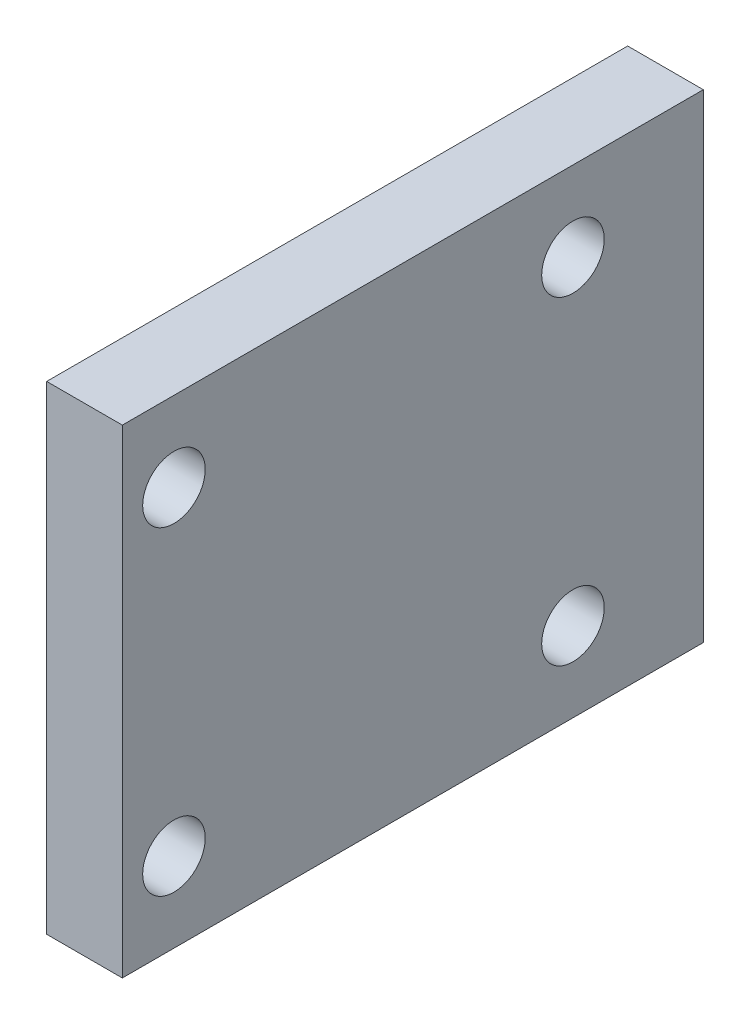
SolidWorks part; units mm, degrees
material "6061 Alloy"
ref_plane "Front Plane" through (0, 0, 0) normal (0, 0, 1) x (1, 0, 0)
ref_plane "Top Plane" through (0, 0, 0) normal (0, 1, 0) x (1, 0, 0)
ref_plane "Right Plane" through (0, 0, 0) normal (1, 0, 0) x (0, 0, -1)
sketch "Sketch2" plane through (-488.9654, 0, 0) normal (1, 0, 0) x (0, 0, -1)
  line L1 (194.9873, 128.4838) -> (194.9873, 166.5838)
  line L2 (194.9873, 126.5338) -> (194.9873, 131.5338) construction
  line L3 (210.0161, 128.4838) -> (140.1661, 128.4838) construction
  line L4 (194.9873, 167.5338) -> (194.9873, 165.7338) construction
  line L5 (140.1661, 166.5838) -> (210.0161, 166.5838) construction
  line L6 (194.9873, 166.5838) -> (148.7593, 166.5838)
  line L7 (148.7593, 166.5838) -> (148.7593, 128.4838)
  line L8 (194.9873, 128.4838) -> (148.7593, 128.4838)
  dimension "D1" = 46.228
extrude "Boss-Extrude1" add sketch "Sketch2" along normal blind 6.0198
hole_wizard "#10 Clearance Hole1" positions "Sketch3" profile "Sketch4" hole size "#10" standard "ANSI Inch"
sketch "Sketch3" plane through (-488.9654, 0, 0) normal (-1, 0, 0) x (0, 0, 1)
  point P0 (-184.6161, 160.2338)
  point P3 (-152.8661, 160.2338)
  point P6 (-152.8661, 134.8338)
  point P9 (-184.6161, 134.8338)
sketch "Sketch4" plane through (-488.9654, 160.2338, -184.6161) normal (0, 1, 0) x (0, 0, 1)
  line L0 (0, 0) -> (0, 26.8957)
  line L1 (0, 26.8957) -> (2.4892, 25.4)
  line L2 (2.4892, 25.4) -> (2.4892, 0)
  line L5 (2.4892, 0) -> (0, 0)
  line L10 (0, 26.8957) -> (-2.4892, 25.4) construction
  line L11 (0, -6.35) -> (0, 107.95) construction
  dimension "Hole Dia." = 4.9784
  dimension "Hole Depth" = 25.4
  dimension "Drill Angle" = 118
